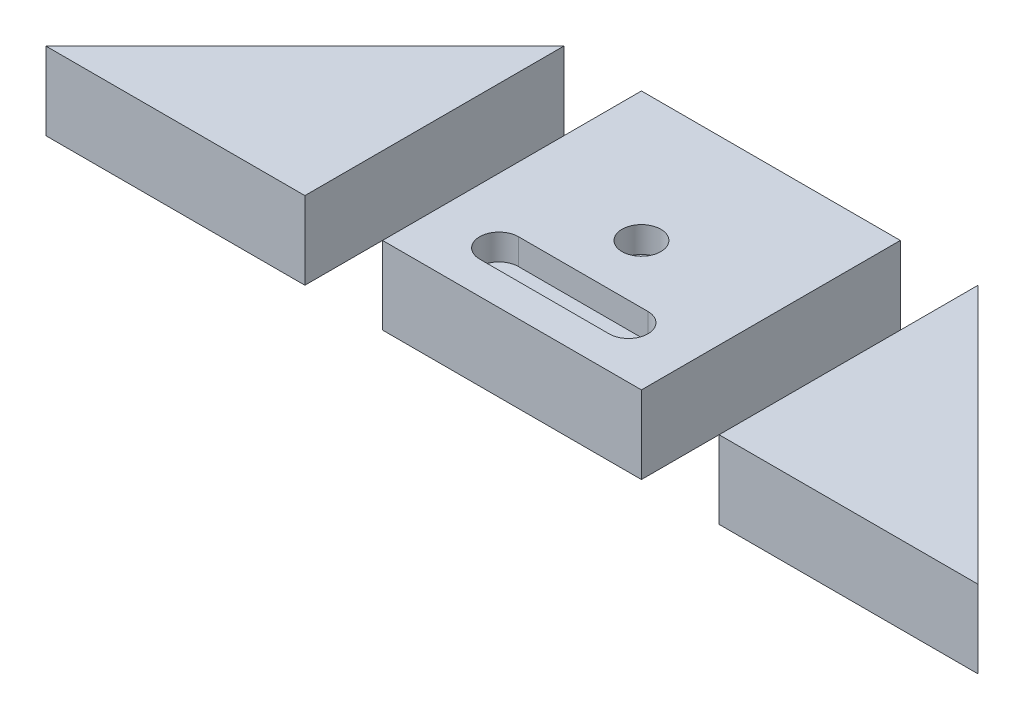
SolidWorks part; units mm, degrees
ref_plane "前视基准面" through (0, 0, 0) normal (0, 0, 1) x (1, 0, 0)
ref_plane "上视基准面" through (0, 0, 0) normal (0, 1, 0) x (1, 0, 0)
ref_plane "右视基准面" through (0, 0, 0) normal (1, 0, 0) x (0, 0, -1)
sketch "草图2" plane through (0, 0, 0) normal (0, 1, 0) x (1, 0, 0)
  line L0 (80, -50) -> (180, -50)
  line L1 (-50, -50) -> (50, -50)
  line L2 (-50, -50) -> (-50, 50)
  line L3 (-50, 50) -> (50, 50)
  line L4 (50, -50) -> (50, 50)
  line L5 (-50, -50) -> (50, 50) construction
  line L6 (-50, 50) -> (50, -50) construction
  line L7 (180, -50) -> (80, 50)
  line L8 (80, 50) -> (80, -50)
  point P0 (0, 0)
  dimension "D1" = 100
  dimension "D2" = 100
  dimension "D3" = 30
extrude "凸台-拉伸1" add sketch "草图2" along normal blind 30
ref_axis "基准轴1" through (0, 0, 0) along (0, 1, 0)
mirror "镜向4" about plane through (0, 0, 0) normal (1, 0, 0) of bodies 107
sketch "草图10" plane through (0, 30, 0) normal (0, 1, 0) x (1, 0, 0)
  line L0 (-25, -30) -> (25, -30) construction
  line L1 (-25, -22.5) -> (25, -22.5)
  line L2 (-25, -37.5) -> (25, -37.5)
  line L3 (0, -30) -> (0, 0) construction
  circle A0 centre (0, 0) radius 7.5
  arc A1 (-25, -22.5) -> (-25, -37.5) centre (-25, -30) ccw
  arc A2 (25, -37.5) -> (25, -22.5) centre (25, -30) ccw
  point P5 (0, -30)
  dimension "D1" = 15
  dimension "D2" = 15
  dimension "D3" = 50
  dimension "D4" = 30
extrude "切除-拉伸1" cut sketch "草图10" against normal blind 10
